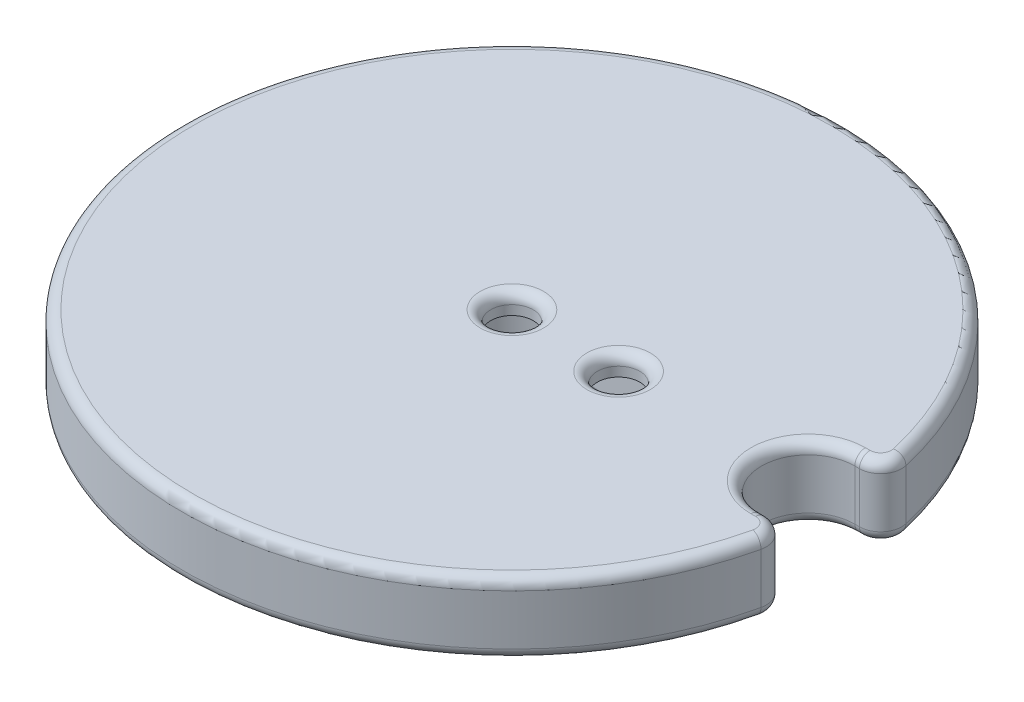
SolidWorks part; units mm, degrees
ref_plane "Front Plane" through (0, 0, 0) normal (0, 0, 1) x (1, 0, 0)
ref_plane "Top Plane" through (0, 0, 0) normal (0, 1, 0) x (1, 0, 0)
ref_plane "Right Plane" through (0, 0, 0) normal (1, 0, 0) x (0, 0, -1)
sketch "Sketch1" plane through (0, 0, 0) normal (0, 1, 0) x (1, 0, 0)
  line L0 (2.2864, 2.65) -> (14.1103, 1.997)
  line L1 (2.2864, -2.65) -> (14.1103, -1.997)
  line L2 (0, 0) -> (14, 0) construction
  line L3 (16, 0) -> (18.725, 0) construction
  line L5 (18.725, 0) -> (24.725, 0) construction
  line L6 (22.225, 3.5) -> (24.476, 3.5)
  line L7 (22.225, -3.5) -> (24.476, -3.5)
  circle A0 centre (0, 0) radius 3.5 construction
  arc A1 (14.1103, 1.997) -> (14.1103, -1.997) centre (14, 0) cw
  arc A2 (2.2864, 2.65) -> (2.2864, -2.65) centre (0, 0) ccw
  circle A3 centre (14, 0) radius 0.5 construction
  circle A4 centre (12, 0) radius 0.5 construction
  circle A5 centre (10, 0) radius 0.5 construction
  circle A6 centre (8, 0) radius 0.5 construction
  circle A7 centre (6, 0) radius 0.5 construction
  circle A8 centre (4, 0) radius 0.5 construction
  arc A9 (-24.725, 0) -> (24.476, 3.5) centre (0, 0) cw
  arc A11 (22.225, 3.5) -> (22.225, -3.5) centre (22.225, 0) ccw
  arc A15 (-24.725, 0) -> (24.476, -3.5) centre (0, 0) ccw
  point P4 (16, 0)
  point P6 (-3.5, 0)
  point P22 (-24.7245, 0)
  point P23 (-24.7229, -0.3256)
  dimension "D1" = 7
  dimension "D5" = 1
  dimension "D10" = 3.5
  dimension "D4" = 2
  dimension "D2" = 19.5
  dimension "D3" = 5.3
  dimension "D7" = 2
  dimension "D9" = 6
  dimension "D12" = 22.225
  dimension "D6" = 6
extrude "Boss-Extrude1" add sketch "Sketch1" along normal blind 4.5
sketch "Sketch2" plane through (0, 4.5, 0) normal (0, 1, 0) x (1, 0, 0)
  line L0 (0, 0) -> (16, 0) construction
  line L6 (24.476, -3.5) -> (22.225, -3.5)
  line L7 (22.225, 3.5) -> (24.476, 3.5)
  line L10 (24.476, -3.5) -> (22.225, -3.5)
  line L11 (22.225, 3.5) -> (24.476, 3.5)
  circle A0 centre (0, 0) radius 1.5875
  circle A1 centre (8, 0) radius 1.5875
  arc A2 (14.1103, -1.997) -> (14.1103, 1.997) centre (14, 0) ccw construction
  arc A11 (24.476, 3.5) -> (24.476, -3.5) centre (0, 0) ccw
  arc A13 (22.225, 3.5) -> (22.225, -3.5) centre (22.225, 0) ccw
  arc A19 (24.476, 3.5) -> (24.476, -3.5) centre (0, 0) ccw
  arc A21 (22.225, 3.5) -> (22.225, -3.5) centre (22.225, 0) ccw
  point P15 (8, 0)
  dimension "D2" = 3.175
  dimension "D3" = 3.175
  dimension "D1" = 0
extrude "Boss-Extrude2" add sketch "Sketch2" along normal offset from surface (1.5 mm away) 6 up to face at (10.1753, 0, 0)
sketch "Sketch3" plane through (0, 0, 0) normal (0, -1, 0) x (1, 0, 0)
  line L4 (24.476, -3.5) -> (22.225, -3.5)
  line L5 (22.225, 3.5) -> (24.476, 3.5)
  line L8 (24.476, -3.5) -> (22.225, -3.5)
  line L9 (22.225, 3.5) -> (24.476, 3.5)
  arc A7 (24.476, 3.5) -> (24.476, -3.5) centre (0, 0) ccw
  arc A8 (22.225, 3.5) -> (22.225, -3.5) centre (22.225, 0) ccw
  arc A13 (24.476, 3.5) -> (24.476, -3.5) centre (0, 0) ccw
  arc A14 (22.225, 3.5) -> (22.225, -3.5) centre (22.225, 0) ccw
  dimension "D1" = 0
extrude "Cut-Extrude1" cut sketch "Sketch3" against normal blind 0.635
fillet "Fillet1" radius 1.5875 2 edges at (24.476, 3.3175, 3.5) (24.476, 3.3175, -3.5)
fillet "Fillet2" radius 0.7937 10 edges at (18.725, 0.635, 0) (22.3981, 0.635, -3.5) (23.8111, 0.635, -4.096) (-24.725, 0.635, 0) (23.8111, 0.635, 4.096) (22.3981, 0.635, 3.5) (-3.5, 0.635, 0) (8.1983, 0.635, -2.3235) (16, 0.635, 0) (8.1983, 0.635, 2.3235)
fillet "Fillet3" radius 0.7937 8 edges at (23.8111, 6, -4.096) (22.3981, 6, -3.5) (18.725, 6, 0) (22.3981, 6, 3.5) (23.8111, 6, 4.096) (-24.725, 6, 0) (0, 6, 1.5875) (8, 6, 1.5875)
